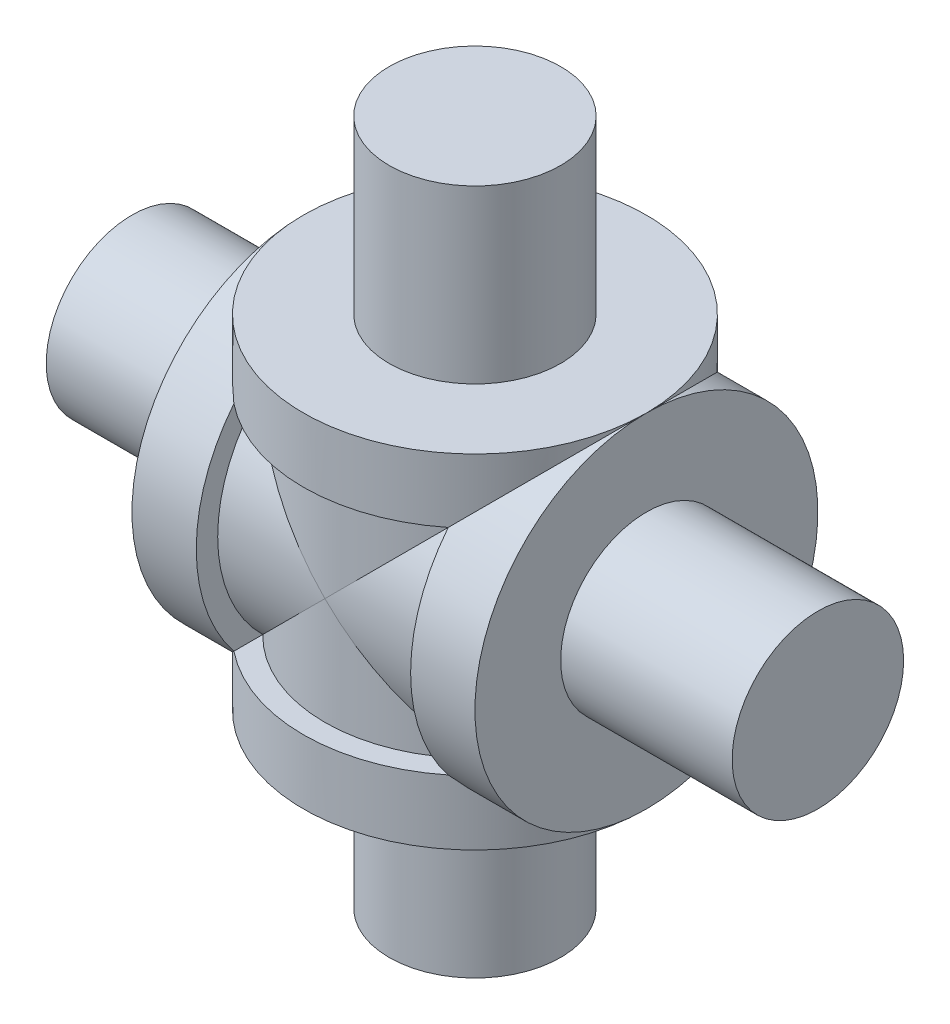
SolidWorks part; units mm, degrees
material "Cast Carbon Steel"
ref_plane "Front Plane" through (0, 0, 0) normal (0, 0, 1) x (1, 0, 0)
ref_plane "Top Plane" through (0, 0, 0) normal (0, 1, 0) x (1, 0, 0)
ref_plane "Right Plane" through (0, 0, 0) normal (1, 0, 0) x (0, 0, -1)
sketch "Sketch1" plane through (0, 0, 0) normal (0, 0, 1) x (1, 0, 0)
  line L0 (-80, 80) -> (-80, -80) construction
  line L1 (0, 0) -> (-80, 0) construction
  line L2 (-80, 80) -> (80, 80) construction
  line L3 (80, 80) -> (80, -80) construction
  line L4 (80, -80) -> (-80, -80) construction
  line L5 (0, 0) -> (0, 95.5066) construction
  line L6 (-80, 0) -> (-80, 20)
  line L8 (-40, 20) -> (-40, 40)
  line L11 (-25, 35) -> (25, 35)
  line L12 (0, 35) -> (0, 0)
  line L13 (0, 0) -> (-80, 0)
  line L14 (-80, 20) -> (-40, 20)
  line L15 (-40, 40) -> (-25, 40)
  line L16 (-25, 40) -> (-25, 35)
  line L17 (0, 0) -> (-122.4582, -122.4582) construction
  line L18 (0, -80) -> (20, -80)
  line L19 (20, -80) -> (20, -40)
  line L20 (20, -40) -> (40, -40)
  line L21 (40, -40) -> (40, -25)
  line L22 (40, -25) -> (35, -25)
  line L23 (35, -25) -> (35, 25)
  line L24 (35, 0) -> (0, 0)
  line L25 (0, 80) -> (0, -80)
  line L26 (40, 20) -> (40, 40)
  line L27 (40, 40) -> (25, 40)
  line L28 (25, 40) -> (25, 35)
  line L29 (0, 0) -> (80, 0)
  line L30 (80, 0) -> (80, 20)
  line L31 (80, 20) -> (40, 20)
  line L32 (0, 80) -> (20, 80)
  line L33 (20, 80) -> (20, 40)
  line L34 (20, 40) -> (40, 40)
  line L35 (40, 40) -> (40, 25)
  line L36 (40, 25) -> (35, 25)
  dimension "D1" = 160
  dimension "D2" = 160
  dimension "D3" = 80
  dimension "D4" = 80
  dimension "D5" = 20
  dimension "D6" = 15
  dimension "D7" = 35
  dimension "D8" = 40
  dimension "D9" = 80
revolve "Revolve1" add sketch "Sketch1" angle 360 about L13 region at (-34.478, 15.522, 0) region at (19.0741, 19.0741, 0) region at (56.9595, 10.3378, 0)
revolve "Revolve3" add sketch "Sketch1<4>" angle 360 about L25 region at (19.0741, 19.0741, 0) region at (15.522, -34.478, 0) region at (10.3378, 56.9595, 0)
sketch "Sketch1<4>" plane through (0, 0, 0) normal (0, 0, 1) x (1, 0, 0) same geometry as "Sketch1"
